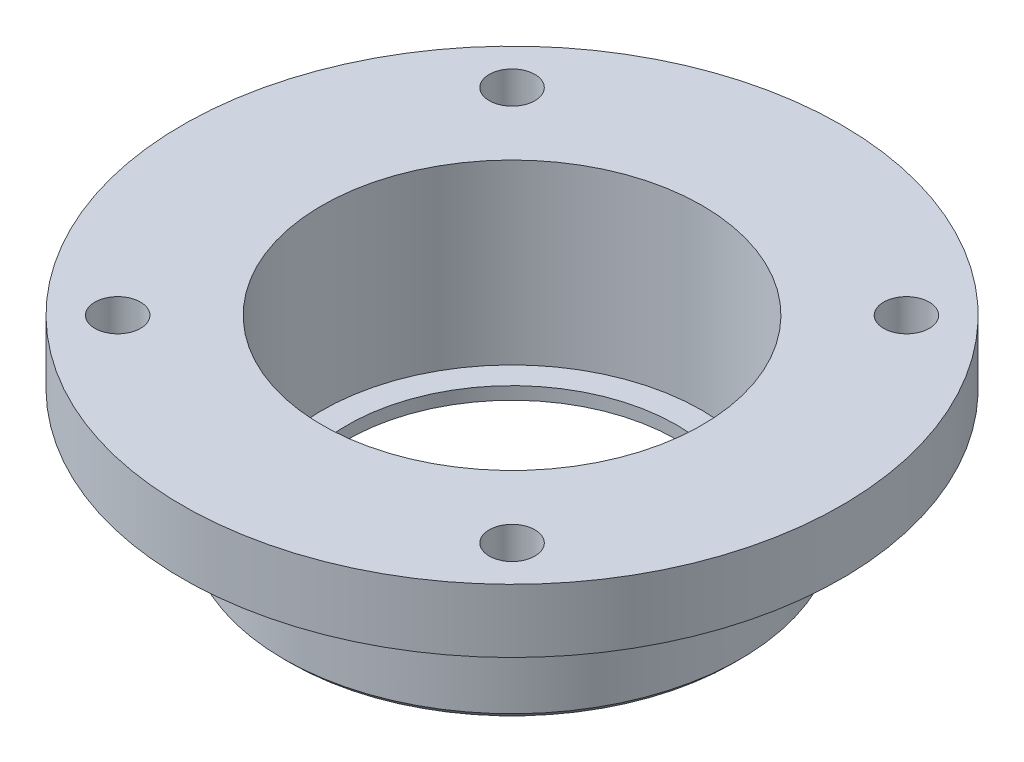
SolidWorks part; units mm, degrees
ref_plane "Спереди" through (0, 0, 0) normal (0, 0, 1) x (1, 0, 0)
ref_plane "Сверху" through (0, 0, 0) normal (0, 1, 0) x (1, 0, 0)
ref_plane "Справа" through (0, 0, 0) normal (1, 0, 0) x (0, 0, -1)
sketch "Эскиз1" plane through (0, 0, 0) normal (0, 0, 1) x (1, 0, 0)
  line L0 (0, 0) -> (0, 8.0722) construction
  line L1 (-15, 1) -> (-15, 15)
  line L2 (-15, 15) -> (-26, 15)
  line L3 (-26, 15) -> (-26, 10)
  line L4 (-26, 10) -> (-18, 10)
  line L5 (-18, 10) -> (-18, 0)
  line L6 (-18, 0) -> (-13, 0)
  line L7 (-13, 0) -> (-13, 1)
  line L8 (-13, 1) -> (-15, 1)
  line L12 (-15, 14.4) -> (15, 14.4) construction
  line L13 (-15, 14.4) -> (15, 14.4) construction
  line L14 (14.4, 15) -> (-14.4, 15) construction
  dimension "D1" = 1
  dimension "D2" = 3
  dimension "D3" = 8
  dimension "D4" = 30
  dimension "D5" = 30
  dimension "D6" = 2
  dimension "D7" = 5
revolve "Повернуть1" add sketch "Эскиз1" angle 360 about L0
chamfer "Фаска1" distance 0.5 angle 45 1 edges at (0, 0, -18)
hole_wizard "Отверстие с зазором M31" positions "Эскиз2" profile "Эскиз3" hole size "M3" standard "DIN" end condition up to next
sketch "Эскиз2" plane through (0, 15, 0) normal (0, 1, 0) x (1, 0, 0)
  line L1 (12.7279, -12.7279) -> (18.3848, -18.3848) construction
  line L3 (0, 0) -> (50000, 0) construction
  circle A1 centre (0, 0) radius 26 construction
  circle A2 centre (0, 0) radius 18 construction
  circle A3 centre (0, 0) radius 26 construction
  circle A4 centre (0, 0) radius 18 construction
  circle A5 centre (0, 0) radius 26 construction
  point P39 (15.5563, -15.5563)
  dimension "D1" = 45
sketch "Эскиз3" plane through (15.5563, 15, 15.5563) normal (1, 0, 0) x (0, 0, 1)
  line L0 (0, 0) -> (0, 5)
  line L1 (0, 5) -> (1.8, 5)
  line L2 (1.8, 5) -> (1.8, 0)
  line L5 (1.8, 0) -> (0, 0)
  line L11 (0, -6.35) -> (0, 107.95) construction
  dimension "Диаметр сквозного отверстия" = 3.6
  dimension "Глубина сквозного отверстия" = 5
pattern_circular "Круговой массив1" count 4 over 360 about axis through (0, 0, 0) along (0, -1, 0) of "Отверстие с зазором M31" reverse direction yes
equation "\"D5@Эскиз1\"=\"D4@Эскиз1\""
